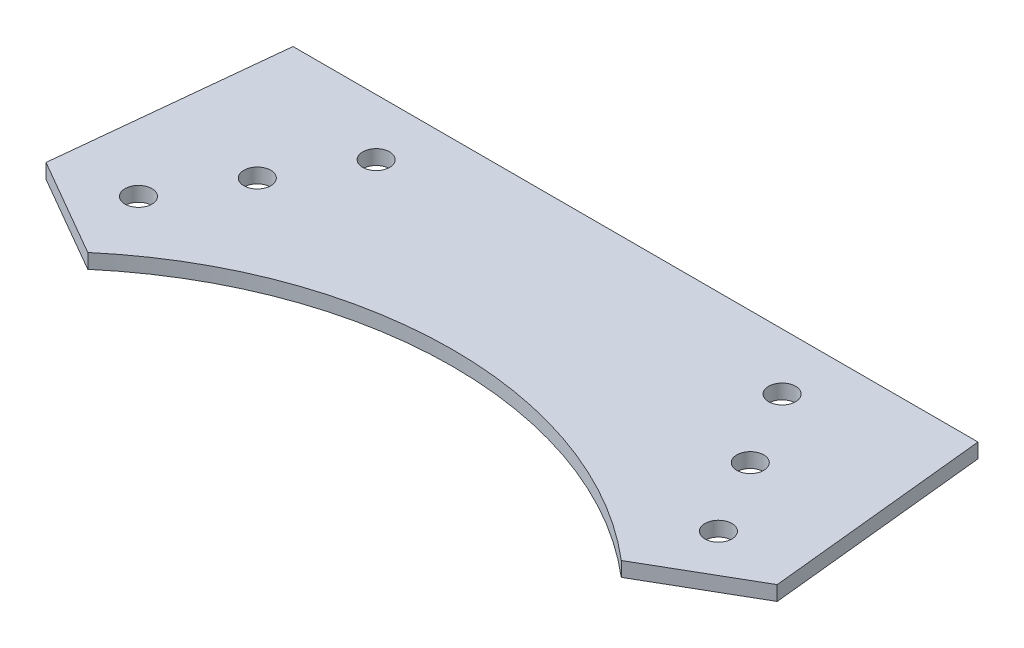
SolidWorks part; units mm, degrees
material "FR4_stuffedProtoboard"
ref_plane "Front Plane" through (0, 0, 0) normal (0, 0, 1) x (1, 0, 0)
ref_plane "Top Plane" through (0, 0, 0) normal (0, 1, 0) x (1, 0, 0)
ref_plane "Right Plane" through (0, 0, 0) normal (1, 0, 0) x (0, 0, -1)
sketch "Sketch1" plane through (0, 0, 0) normal (0, 1, 0) x (1, 0, 0)
  line L0 (-37.5, -32.3215) -> (37.5, -32.3215)
  line L1 (0, 0) -> (-34.6193, -59.9625) construction
  line L2 (0, 0) -> (34.6193, -59.9625) construction
  line L3 (-40.032, -56.8375) -> (-29.2067, -63.0875)
  line L4 (-40.032, -56.8375) -> (-37.5, -32.3215)
  line L5 (0, 0) -> (0, -62.6175) construction
  line L6 (40.032, -56.8375) -> (29.2067, -63.0875)
  line L7 (40.032, -56.8375) -> (37.5, -32.3215)
  arc A0 (-29.2067, -63.0875) -> (29.2067, -63.0875) centre (0, -97.3215) cw
  point P2 (0, -32.3215)
  point P7 (0, -52.3215)
  dimension "D3" = 45
  dimension "D4" = 65
  dimension "D1" = 32.3215
  dimension "D2" = 75
  dimension "D5" = 60
  dimension "D6" = 12.5
extrude "Boss-Extrude1" add sketch "Sketch1" along normal blind 1.6
hole_wizard "#4 Clearance Hole1" positions "Sketch2" profile "Sketch3" hole size "#4" standard "ANSI Inch" end condition through all
sketch "Sketch2" plane through (0, 1.6, 0) normal (0, 1, 0) x (1, 0, 0)
  line L0 (0, 0) -> (22.225, -38.4948) construction
  line L2 (0, 0) -> (0, -19.1492) construction
  point P0 (22.225, -38.4948)
  point P22 (26.9875, -46.7437)
  point P23 (31.75, -54.9926)
  dimension "D1" = 30
  dimension "D2" = 44.45
  dimension "D4" = 9.525
  dimension "D3" = 3
sketch "Sketch3" plane through (22.225, 1.6, 38.4948) normal (1, 0, 0) x (0, 0, 1)
  line L0 (0, 0) -> (0, 1.6)
  line L1 (0, 1.6) -> (1.4732, 1.6)
  line L2 (1.4732, 1.6) -> (1.4732, 0)
  line L5 (1.4732, 0) -> (0, 0)
  line L11 (0, -6.35) -> (0, 107.95) construction
  dimension "Thru Hole Dia." = 2.9464
  dimension "Thru Hole Depth" = 1.6
mirror "Mirror1" about plane through (0, 0, 0) normal (1, 0, 0) of "#4 Clearance Hole1"
